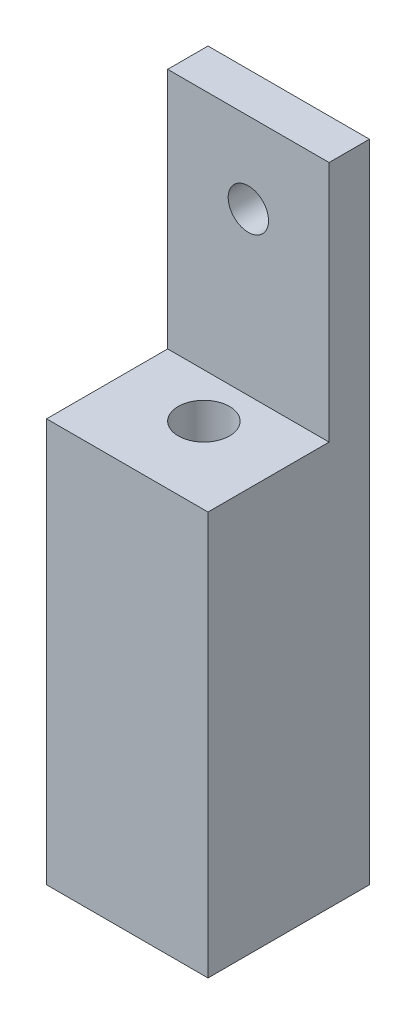
SolidWorks part; units mm, degrees
ref_plane "Front Plane" through (0, 0, 0) normal (0, 0, 1) x (1, 0, 0)
ref_plane "Top Plane" through (0, 0, 0) normal (0, 1, 0) x (1, 0, 0)
ref_plane "Right Plane" through (0, 0, 0) normal (1, 0, 0) x (0, 0, -1)
sketch "Sketch1" plane through (0, 0, 0) normal (0, 1, 0) x (1, 0, 0)
  line L1 (-10, -10) -> (10, -10)
  line L2 (-10, -10) -> (-10, 10)
  line L3 (-10, 10) -> (10, 10)
  line L4 (10, -10) -> (10, 10)
  line L5 (-10, -10) -> (10, 10) construction
  line L6 (-10, 10) -> (10, -10) construction
  circle A1 centre (0, -0.51) radius 3.175
  point P0 (0, 0)
  point P8 (0, 0)
  dimension "D1" = 6.35
  dimension "D2" = 20
  dimension "D3" = 0.51
extrude "Boss-Extrude1" add sketch "Sketch1" along normal mid plane 50
sketch "Sketch2" plane through (0, 25, 0) normal (0, 1, 0) x (1, 0, 0)
  line L0 (10, -10) -> (10, 10) construction
  line L1 (-10, 10) -> (10, 10)
  line L2 (-10, 10) -> (-10, 5)
  line L3 (-10, 5) -> (10, 5)
  line L4 (10, 10) -> (10, 5)
  dimension "D1" = 5
extrude "Boss-Extrude2" add sketch "Sketch2" along normal blind 30
sketch "Sketch3" plane through (0, 0, -5) normal (0, 0, 1) x (1, 0, 0)
  line L0 (0, 55) -> (0, 45) construction
  line L1 (-10, 55) -> (10, 55) construction
  line L2 (0, 45) -> (-10, 45) construction
  line L3 (-10, 55) -> (-10, 25) construction
  circle A0 centre (0, 45) radius 2.5
  dimension "D1" = 5
extrude "Cut-Extrude1" cut sketch "Sketch3" against normal through all
